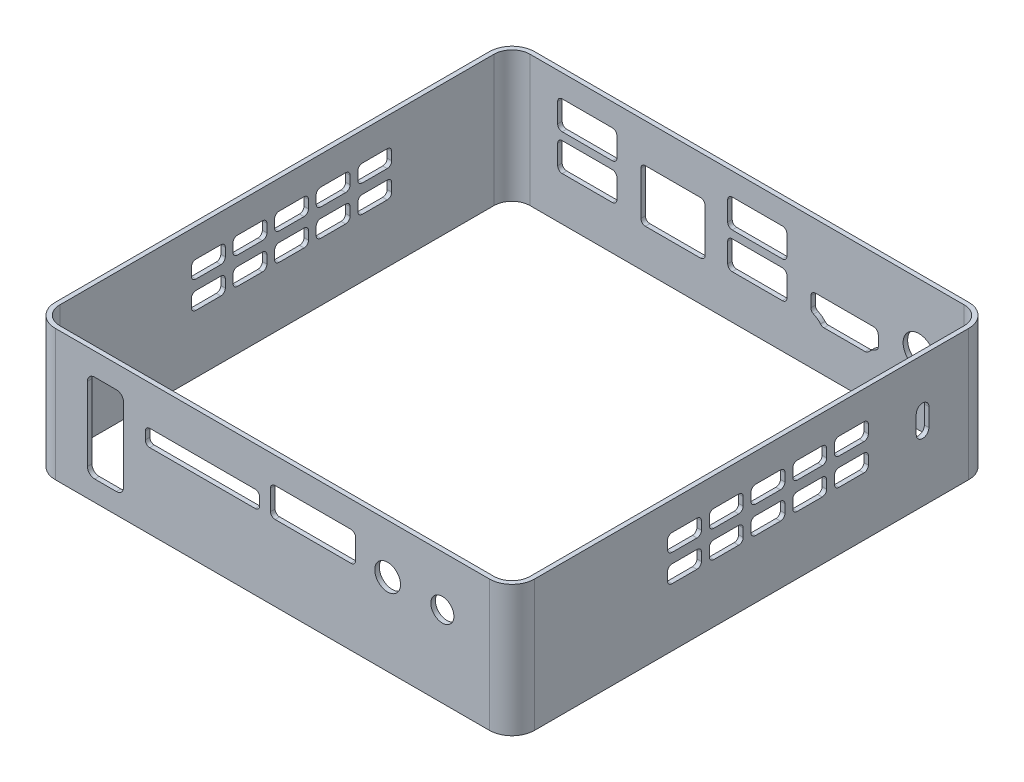
SolidWorks part; units mm, degrees
ref_plane "Front Plane" through (0, 0, 0) normal (0, 0, 1) x (1, 0, 0)
ref_plane "Top Plane" through (0, 0, 0) normal (0, 1, 0) x (1, 0, 0)
ref_plane "Right Plane" through (0, 0, 0) normal (1, 0, 0) x (0, 0, -1)
sketch "Sketch1" plane through (0, 0, 0) normal (0, 1, 0) x (1, 0, 0)
  line L0 (1, 5) -> (1, 101)
  line L1 (5, 0) -> (101, 0)
  line L2 (0, 5) -> (0, 101)
  line L3 (5, 106) -> (101, 106)
  line L4 (106, 5) -> (106, 101)
  line L5 (5, 105) -> (101, 105)
  line L6 (105, 5) -> (105, 101)
  line L7 (5, 1) -> (101, 1)
  arc A0 (101, 0) -> (106, 5) centre (101, 5) ccw
  arc A1 (5, 0) -> (0, 5) centre (5, 5) cw
  arc A2 (101, 106) -> (106, 101) centre (101, 101) cw
  arc A3 (0, 101) -> (5, 106) centre (5, 101) cw
  arc A4 (1, 101) -> (5, 105) centre (5, 101) cw
  arc A5 (101, 105) -> (105, 101) centre (101, 101) cw
  arc A6 (101, 1) -> (105, 5) centre (101, 5) ccw
  arc A7 (5, 1) -> (1, 5) centre (5, 5) cw
  point P9 (0, 0)
  dimension "D3" = 5
  dimension "D1" = 106
  dimension "D2" = 106
  dimension "D4" = 1
extrude "Boss-Extrude1" add sketch "Sketch1" along normal blind 29
sketch "Sketch12" plane through (106, 0, 0) normal (1, 0, 0) x (0, 0, -1)
  line L0 (44.63, 22.7) -> (50.13, 22.7)
  line L1 (35.4, 22.7) -> (40.9, 22.7)
  line L2 (34.4, 21.7) -> (34.4, 19.9)
  line L3 (35.4, 18.9) -> (40.9, 18.9)
  line L4 (41.9, 21.7) -> (41.9, 19.9)
  line L5 (44.63, 18.9) -> (50.13, 18.9)
  line L6 (43.63, 21.7) -> (43.63, 19.9)
  line L7 (51.13, 21.7) -> (51.13, 19.9)
  line L8 (53.86, 22.7) -> (59.36, 22.7)
  line L9 (53.86, 18.9) -> (59.36, 18.9)
  line L10 (52.86, 21.7) -> (52.86, 19.9)
  line L11 (60.36, 21.7) -> (60.36, 19.9)
  line L12 (63.09, 22.7) -> (68.59, 22.7)
  line L13 (63.09, 18.9) -> (68.59, 18.9)
  line L14 (62.09, 21.7) -> (62.09, 19.9)
  line L15 (69.59, 21.7) -> (69.59, 19.9)
  line L16 (72.32, 22.7) -> (77.82, 22.7)
  line L17 (72.32, 18.9) -> (77.82, 18.9)
  line L18 (71.32, 21.7) -> (71.32, 19.9)
  line L19 (78.82, 21.7) -> (78.82, 19.9)
  line L20 (44.63, 16.7) -> (50.13, 16.7)
  line L21 (44.63, 12.9) -> (50.13, 12.9)
  line L22 (43.63, 15.7) -> (43.63, 13.9)
  line L23 (51.13, 15.7) -> (51.13, 13.9)
  line L24 (53.86, 16.7) -> (59.36, 16.7)
  line L25 (53.86, 12.9) -> (59.36, 12.9)
  line L26 (52.86, 15.7) -> (52.86, 13.9)
  line L27 (60.36, 15.7) -> (60.36, 13.9)
  line L28 (63.09, 16.7) -> (68.59, 16.7)
  line L29 (63.09, 12.9) -> (68.59, 12.9)
  line L30 (62.09, 15.7) -> (62.09, 13.9)
  line L31 (69.59, 15.7) -> (69.59, 13.9)
  line L32 (72.32, 16.7) -> (77.82, 16.7)
  line L33 (72.32, 12.9) -> (77.82, 12.9)
  line L34 (71.32, 15.7) -> (71.32, 13.9)
  line L35 (78.82, 15.7) -> (78.82, 13.9)
  line L36 (35.4, 16.7) -> (40.9, 16.7)
  line L37 (35.4, 12.9) -> (40.9, 12.9)
  line L38 (34.4, 15.7) -> (34.4, 13.9)
  line L39 (41.9, 15.7) -> (41.9, 13.9)
  arc A0 (34.4, 19.9) -> (35.4, 18.9) centre (35.4, 19.9) ccw
  arc A1 (40.9, 18.9) -> (41.9, 19.9) centre (40.9, 19.9) ccw
  arc A2 (40.9, 22.7) -> (41.9, 21.7) centre (40.9, 21.7) cw
  arc A3 (35.4, 22.7) -> (34.4, 21.7) centre (35.4, 21.7) ccw
  arc A4 (43.63, 19.9) -> (44.63, 18.9) centre (44.63, 19.9) ccw
  arc A5 (44.63, 22.7) -> (43.63, 21.7) centre (44.63, 21.7) ccw
  arc A6 (50.13, 22.7) -> (51.13, 21.7) centre (50.13, 21.7) cw
  arc A7 (50.13, 18.9) -> (51.13, 19.9) centre (50.13, 19.9) ccw
  arc A8 (52.86, 19.9) -> (53.86, 18.9) centre (53.86, 19.9) ccw
  arc A9 (53.86, 22.7) -> (52.86, 21.7) centre (53.86, 21.7) ccw
  arc A10 (59.36, 22.7) -> (60.36, 21.7) centre (59.36, 21.7) cw
  arc A11 (59.36, 18.9) -> (60.36, 19.9) centre (59.36, 19.9) ccw
  arc A12 (62.09, 19.9) -> (63.09, 18.9) centre (63.09, 19.9) ccw
  arc A13 (63.09, 22.7) -> (62.09, 21.7) centre (63.09, 21.7) ccw
  arc A14 (68.59, 22.7) -> (69.59, 21.7) centre (68.59, 21.7) cw
  arc A15 (68.59, 18.9) -> (69.59, 19.9) centre (68.59, 19.9) ccw
  arc A16 (71.32, 19.9) -> (72.32, 18.9) centre (72.32, 19.9) ccw
  arc A17 (72.32, 22.7) -> (71.32, 21.7) centre (72.32, 21.7) ccw
  arc A18 (77.82, 22.7) -> (78.82, 21.7) centre (77.82, 21.7) cw
  arc A19 (77.82, 18.9) -> (78.82, 19.9) centre (77.82, 19.9) ccw
  arc A20 (43.63, 13.9) -> (44.63, 12.9) centre (44.63, 13.9) ccw
  arc A21 (44.63, 16.7) -> (43.63, 15.7) centre (44.63, 15.7) ccw
  arc A22 (50.13, 16.7) -> (51.13, 15.7) centre (50.13, 15.7) cw
  arc A23 (50.13, 12.9) -> (51.13, 13.9) centre (50.13, 13.9) ccw
  arc A24 (52.86, 13.9) -> (53.86, 12.9) centre (53.86, 13.9) ccw
  arc A25 (53.86, 16.7) -> (52.86, 15.7) centre (53.86, 15.7) ccw
  arc A26 (59.36, 16.7) -> (60.36, 15.7) centre (59.36, 15.7) cw
  arc A27 (59.36, 12.9) -> (60.36, 13.9) centre (59.36, 13.9) ccw
  arc A28 (62.09, 13.9) -> (63.09, 12.9) centre (63.09, 13.9) ccw
  arc A29 (63.09, 16.7) -> (62.09, 15.7) centre (63.09, 15.7) ccw
  arc A30 (68.59, 16.7) -> (69.59, 15.7) centre (68.59, 15.7) cw
  arc A31 (68.59, 12.9) -> (69.59, 13.9) centre (68.59, 13.9) ccw
  arc A32 (71.32, 13.9) -> (72.32, 12.9) centre (72.32, 13.9) ccw
  arc A33 (72.32, 16.7) -> (71.32, 15.7) centre (72.32, 15.7) ccw
  arc A34 (77.82, 16.7) -> (78.82, 15.7) centre (77.82, 15.7) cw
  arc A35 (77.82, 12.9) -> (78.82, 13.9) centre (77.82, 13.9) ccw
  arc A36 (34.4, 13.9) -> (35.4, 12.9) centre (35.4, 13.9) ccw
  arc A37 (35.4, 16.7) -> (34.4, 15.7) centre (35.4, 15.7) ccw
  arc A38 (40.9, 16.7) -> (41.9, 15.7) centre (40.9, 15.7) cw
  arc A39 (40.9, 12.9) -> (41.9, 13.9) centre (40.9, 13.9) ccw
  dimension "D5" = 1
  dimension "D1" = 3.8
  dimension "D2" = 7.5
  dimension "D3" = 34.4
  dimension "D4" = 18.9
  dimension "D6" = 5
  dimension "D7" = 2
extrude "Cut-Extrude2" cut sketch "Sketch12" against normal blind 2
sketch "Sketch13" plane through (106, 0, 0) normal (1, 0, 0) x (0, 0, -1)
  line L0 (90.8, 14.4) -> (90.8, 18.4) construction
  line L1 (89.4, 14.4) -> (89.4, 18.4)
  line L2 (92.2, 14.4) -> (92.2, 18.4)
  arc A0 (89.4, 14.4) -> (92.2, 14.4) centre (90.8, 14.4) ccw
  arc A1 (92.2, 18.4) -> (89.4, 18.4) centre (90.8, 18.4) ccw
  point P2 (90.8, 16.4)
  dimension "D1" = 1.4
  dimension "D2" = 4
  dimension "D3" = 14.4
  dimension "D4" = 90.8
extrude "Cut-Extrude3" cut sketch "Sketch13" against normal blind 2
sketch "Sketch14" plane through (0, 0, 0) normal (-1, 0, 0) x (0, 0, 1)
  line L0 (-68.2, 22.7) -> (-62.7, 22.7)
  line L1 (-77.4, 22.7) -> (-71.9, 22.7)
  line L2 (-78.4, 21.7) -> (-78.4, 19.9)
  line L3 (-77.4, 18.9) -> (-71.9, 18.9)
  line L4 (-70.9, 21.7) -> (-70.9, 19.9)
  line L5 (-69.2, 21.7) -> (-69.2, 19.9)
  line L6 (-68.2, 18.9) -> (-62.7, 18.9)
  line L7 (-61.7, 21.7) -> (-61.7, 19.9)
  line L8 (-59, 22.7) -> (-53.5, 22.7)
  line L9 (-60, 21.7) -> (-60, 19.9)
  line L10 (-59, 18.9) -> (-53.5, 18.9)
  line L11 (-52.5, 21.7) -> (-52.5, 19.9)
  line L12 (-49.8, 22.7) -> (-44.3, 22.7)
  line L13 (-50.8, 21.7) -> (-50.8, 19.9)
  line L14 (-49.8, 18.9) -> (-44.3, 18.9)
  line L15 (-43.3, 21.7) -> (-43.3, 19.9)
  line L16 (-40.6, 22.7) -> (-35.1, 22.7)
  line L17 (-41.6, 21.7) -> (-41.6, 19.9)
  line L18 (-40.6, 18.9) -> (-35.1, 18.9)
  line L19 (-34.1, 21.7) -> (-34.1, 19.9)
  line L20 (-68.2, 16.7) -> (-62.7, 16.7)
  line L21 (-69.2, 15.7) -> (-69.2, 13.9)
  line L22 (-68.2, 12.9) -> (-62.7, 12.9)
  line L23 (-61.7, 15.7) -> (-61.7, 13.9)
  line L24 (-59, 16.7) -> (-53.5, 16.7)
  line L25 (-60, 15.7) -> (-60, 13.9)
  line L26 (-59, 12.9) -> (-53.5, 12.9)
  line L27 (-52.5, 15.7) -> (-52.5, 13.9)
  line L28 (-49.8, 16.7) -> (-44.3, 16.7)
  line L29 (-50.8, 15.7) -> (-50.8, 13.9)
  line L30 (-49.8, 12.9) -> (-44.3, 12.9)
  line L31 (-43.3, 15.7) -> (-43.3, 13.9)
  line L32 (-40.6, 16.7) -> (-35.1, 16.7)
  line L33 (-41.6, 15.7) -> (-41.6, 13.9)
  line L34 (-40.6, 12.9) -> (-35.1, 12.9)
  line L35 (-34.1, 15.7) -> (-34.1, 13.9)
  line L36 (-77.4, 16.7) -> (-71.9, 16.7)
  line L37 (-78.4, 15.7) -> (-78.4, 13.9)
  line L38 (-77.4, 12.9) -> (-71.9, 12.9)
  line L39 (-70.9, 15.7) -> (-70.9, 13.9)
  arc A0 (-71.9, 18.9) -> (-70.9, 19.9) centre (-71.9, 19.9) ccw
  arc A1 (-71.9, 22.7) -> (-70.9, 21.7) centre (-71.9, 21.7) cw
  arc A2 (-77.4, 22.7) -> (-78.4, 21.7) centre (-77.4, 21.7) ccw
  arc A3 (-78.4, 19.9) -> (-77.4, 18.9) centre (-77.4, 19.9) ccw
  arc A4 (-62.7, 18.9) -> (-61.7, 19.9) centre (-62.7, 19.9) ccw
  arc A5 (-62.7, 22.7) -> (-61.7, 21.7) centre (-62.7, 21.7) cw
  arc A6 (-68.2, 22.7) -> (-69.2, 21.7) centre (-68.2, 21.7) ccw
  arc A7 (-69.2, 19.9) -> (-68.2, 18.9) centre (-68.2, 19.9) ccw
  arc A8 (-53.5, 18.9) -> (-52.5, 19.9) centre (-53.5, 19.9) ccw
  arc A9 (-53.5, 22.7) -> (-52.5, 21.7) centre (-53.5, 21.7) cw
  arc A10 (-59, 22.7) -> (-60, 21.7) centre (-59, 21.7) ccw
  arc A11 (-60, 19.9) -> (-59, 18.9) centre (-59, 19.9) ccw
  arc A12 (-44.3, 18.9) -> (-43.3, 19.9) centre (-44.3, 19.9) ccw
  arc A13 (-44.3, 22.7) -> (-43.3, 21.7) centre (-44.3, 21.7) cw
  arc A14 (-49.8, 22.7) -> (-50.8, 21.7) centre (-49.8, 21.7) ccw
  arc A15 (-50.8, 19.9) -> (-49.8, 18.9) centre (-49.8, 19.9) ccw
  arc A16 (-35.1, 18.9) -> (-34.1, 19.9) centre (-35.1, 19.9) ccw
  arc A17 (-35.1, 22.7) -> (-34.1, 21.7) centre (-35.1, 21.7) cw
  arc A18 (-40.6, 22.7) -> (-41.6, 21.7) centre (-40.6, 21.7) ccw
  arc A19 (-41.6, 19.9) -> (-40.6, 18.9) centre (-40.6, 19.9) ccw
  arc A20 (-62.7, 12.9) -> (-61.7, 13.9) centre (-62.7, 13.9) ccw
  arc A21 (-62.7, 16.7) -> (-61.7, 15.7) centre (-62.7, 15.7) cw
  arc A22 (-68.2, 16.7) -> (-69.2, 15.7) centre (-68.2, 15.7) ccw
  arc A23 (-69.2, 13.9) -> (-68.2, 12.9) centre (-68.2, 13.9) ccw
  arc A24 (-53.5, 12.9) -> (-52.5, 13.9) centre (-53.5, 13.9) ccw
  arc A25 (-53.5, 16.7) -> (-52.5, 15.7) centre (-53.5, 15.7) cw
  arc A26 (-59, 16.7) -> (-60, 15.7) centre (-59, 15.7) ccw
  arc A27 (-60, 13.9) -> (-59, 12.9) centre (-59, 13.9) ccw
  arc A28 (-44.3, 12.9) -> (-43.3, 13.9) centre (-44.3, 13.9) ccw
  arc A29 (-44.3, 16.7) -> (-43.3, 15.7) centre (-44.3, 15.7) cw
  arc A30 (-49.8, 16.7) -> (-50.8, 15.7) centre (-49.8, 15.7) ccw
  arc A31 (-50.8, 13.9) -> (-49.8, 12.9) centre (-49.8, 13.9) ccw
  arc A32 (-35.1, 12.9) -> (-34.1, 13.9) centre (-35.1, 13.9) ccw
  arc A33 (-35.1, 16.7) -> (-34.1, 15.7) centre (-35.1, 15.7) cw
  arc A34 (-40.6, 16.7) -> (-41.6, 15.7) centre (-40.6, 15.7) ccw
  arc A35 (-41.6, 13.9) -> (-40.6, 12.9) centre (-40.6, 13.9) ccw
  arc A36 (-71.9, 12.9) -> (-70.9, 13.9) centre (-71.9, 13.9) ccw
  arc A37 (-71.9, 16.7) -> (-70.9, 15.7) centre (-71.9, 15.7) cw
  arc A38 (-77.4, 16.7) -> (-78.4, 15.7) centre (-77.4, 15.7) ccw
  arc A39 (-78.4, 13.9) -> (-77.4, 12.9) centre (-77.4, 13.9) ccw
  dimension "D3" = 1
  dimension "D1" = 3.8
  dimension "D2" = 7.5
  dimension "D4" = 18.9
  dimension "D5" = 78.4
  dimension "D6" = 5
  dimension "D7" = 2
extrude "Cut-Extrude4" cut sketch "Sketch14" against normal blind 2
sketch "Sketch15" plane through (0, 0, 0) normal (0, 0, 1) x (1, 0, 0)
  line L1 (49.2, 20.3) -> (25.9, 20.3)
  line L2 (50.2, 19.3) -> (50.2, 17.6)
  line L3 (49.2, 16.6) -> (25.9, 16.6)
  line L4 (24.9, 19.3) -> (24.9, 17.6)
  line L5 (53.6, 23.2) -> (70.4, 23.2)
  line L6 (52.6, 22.2) -> (52.6, 17.7)
  line L7 (53.6, 16.7) -> (70.4, 16.7)
  line L8 (71.4, 22.2) -> (71.4, 17.7)
  circle A0 centre (78.5, 18.1) radius 2.85
  circle A1 centre (90.6, 17.9) radius 2.55
  arc A2 (70.4, 16.7) -> (71.4, 17.7) centre (70.4, 17.7) ccw
  arc A3 (70.4, 23.2) -> (71.4, 22.2) centre (70.4, 22.2) cw
  arc A4 (53.6, 23.2) -> (52.6, 22.2) centre (53.6, 22.2) ccw
  arc A5 (52.6, 17.7) -> (53.6, 16.7) centre (53.6, 17.7) ccw
  arc A6 (50.2, 17.6) -> (49.2, 16.6) centre (49.2, 17.6) cw
  arc A7 (49.2, 20.3) -> (50.2, 19.3) centre (49.2, 19.3) cw
  arc A8 (25.9, 16.6) -> (24.9, 17.6) centre (25.9, 17.6) cw
  arc A9 (25.9, 20.3) -> (24.9, 19.3) centre (25.9, 19.3) ccw
  dimension "D13" = 5.7
  dimension "D14" = 5.1
  dimension "D15" = 1
  dimension "D1" = 3.7
  dimension "D2" = 25.3
  dimension "D3" = 16.6
  dimension "D4" = 24.9
  dimension "D5" = 6.5
  dimension "D6" = 18.8
  dimension "D7" = 52.6
  dimension "D8" = 16.7
  dimension "D9" = 18.1
  dimension "D10" = 78.5
  dimension "D11" = 90.6
  dimension "D12" = 17.9
extrude "Cut-Extrude5" cut sketch "Sketch15" against normal blind 2
sketch "Sketch16" plane through (0, 0, -106) normal (0, 0, -1) x (-1, 0, 0)
  line L0 (-81, 14.8) -> (-68.1, 14.8)
  line L1 (-67.1, 13.8) -> (-67.1, 11.493)
  line L2 (-69.9908, 9.1) -> (-79.1092, 9.1)
  line L3 (-82, 11.493) -> (-82, 13.8)
  line L4 (-24.2, 23) -> (-24.2, 18.7)
  line L5 (-60.8, 24) -> (-49.7, 24)
  line L6 (-61.8, 23) -> (-61.8, 18.7)
  line L7 (-60.8, 17.7) -> (-49.7, 17.7)
  line L8 (-48.7, 23) -> (-48.7, 18.7)
  line L9 (-42.7, 20.4) -> (-30.5, 20.4)
  line L10 (-43.7, 19.4) -> (-43.7, 9.8)
  line L11 (-42.7, 8.8) -> (-30.5, 8.8)
  line L12 (-29.5, 19.4) -> (-29.5, 9.8)
  line L13 (-23.2, 24) -> (-12.1, 24)
  line L14 (-11.1, 23) -> (-11.1, 18.7)
  line L15 (-23.2, 17.7) -> (-12.1, 17.7)
  line L16 (-24.2, 15) -> (-24.2, 10.7)
  line L17 (-23.2, 16) -> (-12.1, 16)
  line L18 (-11.1, 15) -> (-11.1, 10.7)
  line L19 (-23.2, 9.7) -> (-12.1, 9.7)
  line L20 (-61.8, 15) -> (-61.8, 10.7)
  line L21 (-60.8, 16) -> (-49.7, 16)
  line L22 (-48.7, 15) -> (-48.7, 10.7)
  line L23 (-60.8, 9.7) -> (-49.7, 9.7)
  circle A0 centre (-91, 15) radius 3.5
  arc A1 (-67.704, 10.5747) -> (-69.2311, 9.4496) centre (-66.0408, 6.7181) ccw
  arc A2 (-79.8689, 9.4496) -> (-81.396, 10.5747) centre (-83.0592, 6.7181) ccw
  arc A3 (-43.7, 9.8) -> (-42.7, 8.8) centre (-42.7, 9.8) ccw
  arc A4 (-30.5, 8.8) -> (-29.5, 9.8) centre (-30.5, 9.8) ccw
  arc A5 (-30.5, 20.4) -> (-29.5, 19.4) centre (-30.5, 19.4) cw
  arc A6 (-42.7, 20.4) -> (-43.7, 19.4) centre (-42.7, 19.4) ccw
  arc A7 (-49.7, 24) -> (-48.7, 23) centre (-49.7, 23) cw
  arc A8 (-49.7, 17.7) -> (-48.7, 18.7) centre (-49.7, 18.7) ccw
  arc A9 (-61.8, 18.7) -> (-60.8, 17.7) centre (-60.8, 18.7) ccw
  arc A10 (-60.8, 24) -> (-61.8, 23) centre (-60.8, 23) ccw
  arc A11 (-81.396, 10.5747) -> (-82, 11.493) centre (-81, 11.493) cw
  arc A12 (-79.1092, 9.1) -> (-79.8689, 9.4496) centre (-79.1092, 10.1) cw
  arc A13 (-69.2311, 9.4496) -> (-69.9908, 9.1) centre (-69.9908, 10.1) cw
  arc A14 (-67.1, 11.493) -> (-67.704, 10.5747) centre (-68.1, 11.493) cw
  arc A15 (-68.1, 14.8) -> (-67.1, 13.8) centre (-68.1, 13.8) cw
  arc A16 (-81, 14.8) -> (-82, 13.8) centre (-81, 13.8) ccw
  arc A17 (-23.2, 24) -> (-24.2, 23) centre (-23.2, 23) ccw
  arc A18 (-12.1, 24) -> (-11.1, 23) centre (-12.1, 23) cw
  arc A19 (-12.1, 17.7) -> (-11.1, 18.7) centre (-12.1, 18.7) ccw
  arc A20 (-24.2, 18.7) -> (-23.2, 17.7) centre (-23.2, 18.7) ccw
  arc A21 (-23.2, 16) -> (-24.2, 15) centre (-23.2, 15) ccw
  arc A22 (-12.1, 16) -> (-11.1, 15) centre (-12.1, 15) cw
  arc A23 (-12.1, 9.7) -> (-11.1, 10.7) centre (-12.1, 10.7) ccw
  arc A24 (-24.2, 10.7) -> (-23.2, 9.7) centre (-23.2, 10.7) ccw
  arc A25 (-60.8, 16) -> (-61.8, 15) centre (-60.8, 15) ccw
  arc A26 (-49.7, 16) -> (-48.7, 15) centre (-49.7, 15) cw
  arc A27 (-49.7, 9.7) -> (-48.7, 10.7) centre (-49.7, 10.7) ccw
  arc A28 (-61.8, 10.7) -> (-60.8, 9.7) centre (-60.8, 10.7) ccw
  point P40 (-79.6, 9.1)
  point P43 (-69.5, 9.1)
  dimension "D1" = 7
  dimension "D5" = 4.2
  dimension "D19" = 1
  dimension "D2" = 2.4
  dimension "D3" = 2.4
  dimension "D4" = 5.7
  dimension "D6" = 91
  dimension "D7" = 15
  dimension "D8" = 67.1
  dimension "D9" = 9.1
  dimension "D10" = 14.9
  dimension "D11" = 6.3
  dimension "D12" = 13.1
  dimension "D13" = 11.6
  dimension "D14" = 14.2
  dimension "D15" = 48.7
  dimension "D16" = 17.7
  dimension "D17" = 29.5
  dimension "D18" = 8.8
  dimension "D20" = 2
  dimension "D21" = 2
extrude "Cut-Extrude6" cut sketch "Sketch16" against normal blind 2
sketch "Sketch17" plane through (0, 0, 0) normal (0, 0, 1) x (1, 0, 0)
  line L1 (13.7, 24) -> (18.5, 24)
  line L2 (12.1, 22.4) -> (12.1, 6.1)
  line L3 (13.7, 4.5) -> (18.5, 4.5)
  line L4 (20.1, 22.4) -> (20.1, 6.1)
  arc A0 (12.1, 6.1) -> (13.7, 4.5) centre (13.7, 6.1) ccw
  arc A1 (18.5, 4.5) -> (20.1, 6.1) centre (18.5, 6.1) ccw
  arc A2 (18.5, 24) -> (20.1, 22.4) centre (18.5, 22.4) cw
  arc A3 (13.7, 24) -> (12.1, 22.4) centre (13.7, 22.4) ccw
  dimension "D5" = 1.6
  dimension "D1" = 8
  dimension "D2" = 19.5
  dimension "D3" = 12.1
  dimension "D4" = 4.5
extrude "Cut-Extrude7" cut sketch "Sketch17" against normal up to next
